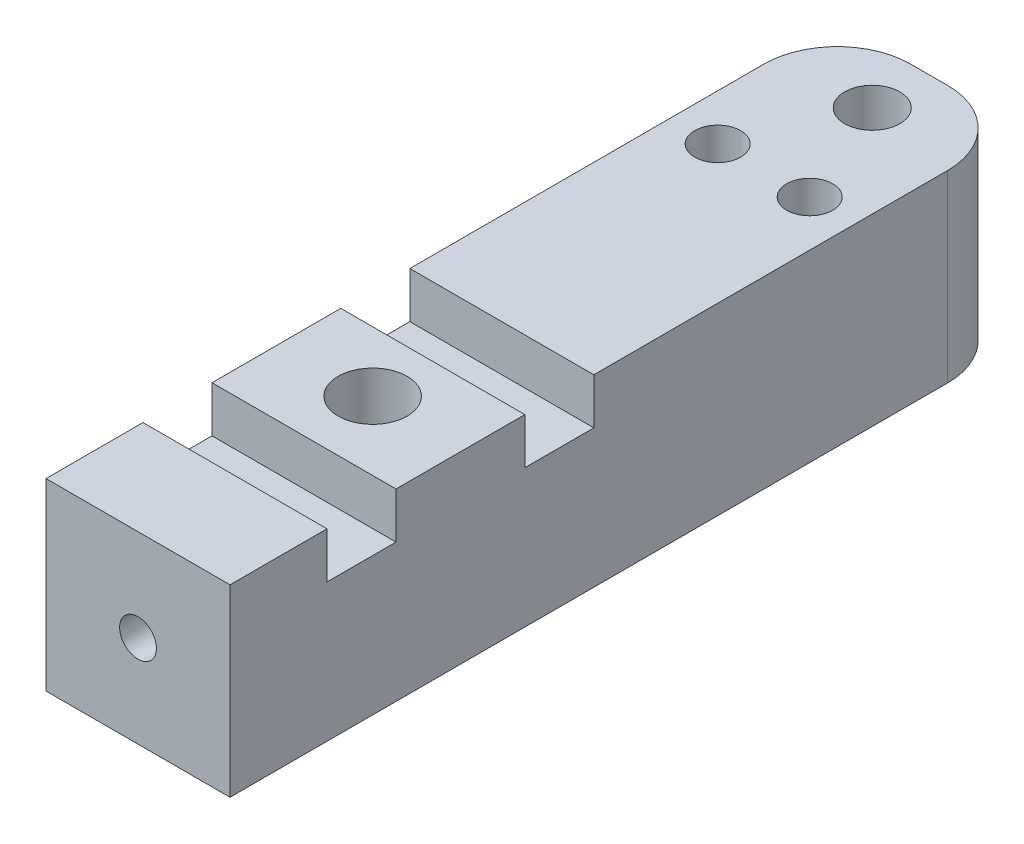
SolidWorks part; units mm, degrees
ref_plane "Front Plane" through (0, 0, 0) normal (0, 0, 1) x (1, 0, 0)
ref_plane "Top Plane" through (0, 0, 0) normal (0, 1, 0) x (1, 0, 0)
ref_plane "Right Plane" through (0, 0, 0) normal (1, 0, 0) x (0, 0, -1)
sketch "Sketch1" plane through (0, 0, 0) normal (0, 1, 0) x (1, 0, 0)
  line L0 (5, 43) -> (5, 0) construction
  line L1 (0, 0) -> (10, 0)
  line L2 (0, 0) -> (0, 39)
  line L3 (4, 43) -> (6, 43)
  line L4 (10, 0) -> (10, 39)
  line L5 (0, 34) -> (10, 34) construction
  arc A0 (0, 39) -> (4, 43) centre (4, 39) cw
  arc A1 (10, 39) -> (6, 43) centre (6, 39) ccw
  circle A2 centre (2.5, 34) radius 1.25
  circle A3 centre (7.5, 34) radius 1.25
  circle A4 centre (5, 12.75) radius 1.875
  dimension "D3" = 4
  dimension "D5" = 2.5
  dimension "D7" = 3.75
  dimension "D1" = 43
  dimension "D2" = 10
  dimension "D4" = 9
  dimension "D6" = 2.5
  dimension "D8" = 12.75
extrude "Boss-Extrude1" add sketch "Sketch1" along normal blind 10
sketch "Sketch2" plane through (0, 10, 0) normal (0, 1, 0) x (1, 0, 0)
  line L0 (0, 39) -> (0, 0) construction
  line L1 (0, 16.0203) -> (10, 16.0203)
  line L2 (0, 16.0203) -> (0, 19.7703)
  line L3 (0, 19.7703) -> (10, 19.7703)
  line L4 (10, 16.0203) -> (10, 19.7703)
  line L5 (10, 0) -> (10, 39) construction
  line L6 (0, 12.5203) -> (10, 12.5203) construction
  line L7 (0, 0) -> (10, 0) construction
  line L8 (0, 5.2703) -> (10, 5.2703)
  line L9 (10, 9.0203) -> (10, 5.2703)
  line L10 (0, 9.0203) -> (10, 9.0203)
  line L11 (0, 9.0203) -> (0, 5.2703)
  line L12 (5, 0) -> (5, 43) construction
  line L13 (6, 43) -> (4, 43) construction
  circle A0 centre (5, 39.9) radius 1.5
  point P12 (5, 12.5203)
  point P19 (7.8507, 39.3049)
  line M12 (0, 39) -> (0, 0)
  line M14 (10, 0) -> (10, 39)
  dimension "D5" = 3
  dimension "D1" = 12.5203
  dimension "D2" = 3.5
  dimension "D3" = 3.75
  dimension "D4" = 3.1
extrude "Cut-Extrude1" cut sketch "Sketch2" against normal blind 2.5 contours L3 L1 M12 M14 | L10 L8 M12 M14 region at (5, 10, -17.8953) region at (5, 10, -7.1453)
extrude "Cut-Extrude2" cut sketch "Sketch2<3>" against normal blind 6.5 contours A0 region at (5, 10, -39.9)
sketch "Sketch2<3>" plane through (0, 10, 0) normal (0, 1, 0) x (1, 0, 0) same geometry as "Sketch2"
sketch "Sketch3" plane through (0, 0, 0) normal (0, 0, 1) x (1, 0, 0)
  line L0 (5, 5) -> (0, 5) construction
  line L1 (0, 10) -> (0, 0) construction
  line L2 (5, 5) -> (10, 5) construction
  line L3 (10, 10) -> (10, 0) construction
  line L4 (5, 5) -> (5, 10) construction
  line L5 (0, 10) -> (10, 10) construction
  line L6 (5, 5) -> (5, 0) construction
  line L7 (0, 0) -> (10, 0) construction
  circle A0 centre (5, 5) radius 1
  dimension "D1" = 2
extrude "Cut-Extrude3" cut sketch "Sketch3" against normal blind 7
